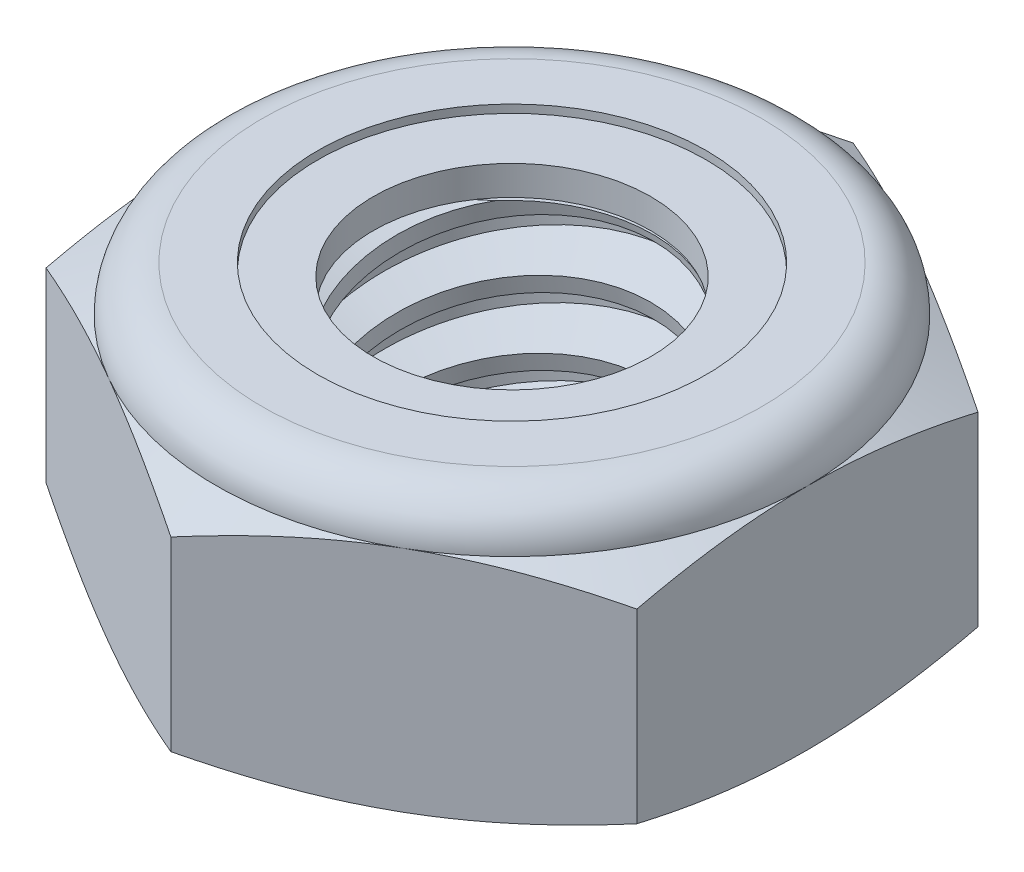
SolidWorks part; units mm, degrees
ref_plane "Front" through (0, 0, 0) normal (0, 0, 1) x (1, 0, 0)
ref_plane "Top" through (0, 0, 0) normal (0, 1, 0) x (1, 0, 0)
ref_plane "Right" through (0, 0, 0) normal (1, 0, 0) x (0, 0, -1)
sketch "Sketch1" plane through (0, 0, 0) normal (0, 1, 0) x (1, 0, 0)
  line L1 (0, 6.4158) -> (-5.5563, 3.2079)
  line L2 (-5.5563, 3.2079) -> (-5.5563, -3.2079)
  line L3 (-5.5563, -3.2079) -> (0, -6.4158)
  line L4 (0, -6.4158) -> (5.5562, -3.2079)
  line L5 (5.5562, -3.2079) -> (5.5562, 3.2079)
  line L6 (5.5562, 3.2079) -> (0, 6.4158)
  circle A0 centre (0, 0) radius 5.5563 construction
  dimension "Hex Flats" = 11.1125
extrude "Extrude1" add sketch "Sketch1" along normal blind 5.1594
sketch "Sketch2" plane through (0, 0, 0) normal (1, 0, 0) x (0, 0, -1)
  line L0 (-3.175, 0) -> (-3.175, 5.1594) construction
  line L1 (0, 0) -> (3.175, 0)
  line L2 (0, 0) -> (0, 5.1594)
  line L3 (0, 5.1594) -> (3.175, 5.1594)
  line L4 (3.175, 0) -> (3.175, 5.1594)
  line L5 (-3.2079, 5.1594) -> (3.2079, 5.1594) construction
  line L7 (0, -3.175) -> (0, 0) construction
  dimension "Thread Dia" = 6.35
revolve "Revolve1" add sketch "Sketch2" angle 360 about L7
sketch "Sketch3" plane through (0, 0, 0) normal (1, 0, 0) x (0, 0, -1)
  line L0 (3.175, 5.1594) -> (-3.175, 5.1594) construction
  line L1 (-3.175, 5.1594) -> (-3.175, 3.8894) construction
  line L2 (-3.175, 3.8894) -> (3.175, 5.1594) construction
  line L3 (3.175, 5.1594) -> (3.2061, 5.0037) construction
  line L4 (3.2061, 5.0037) -> (3.4241, 3.914)
  line L5 (3.4241, 3.914) -> (2.6722, 4.1684)
  line L6 (2.6722, 4.1684) -> (2.6099, 4.4797)
  line L7 (2.6099, 4.4797) -> (3.2061, 5.0037)
  line L8 (2.641, 4.3241) -> (3.3151, 4.4589) construction
  line L9 (3.175, 5.1594) -> (3.175, 4.4309) construction
  line L10 (3.175, 4.4309) -> (-3.175, 3.1609) construction
  line L11 (-3.175, 3.1609) -> (-3.175, 3.8894) construction
  line L12 (-0.2727, 5.1594) -> (0.2727, 2.4323) construction
  line L13 (-3.175, 0) -> (-3.175, 5.1594) construction
  line L14 (0, 5.1594) -> (3.175, 5.1594) construction
  line L15 (3.175, 0) -> (3.175, 5.1594) construction
  point P13 (0, 3.7959)
  dimension "D1" = 0.1588
  dimension "D2" = 0.3175
  dimension "Thread Pitch" = 1.27
  dimension "D4" = 60
  dimension "D5" = 1.27
revolve "Cut-Revolve1" cut sketch "Sketch3" angle 360 about L12
pattern_linear "LPattern1" count 4 spacing 1.27 along (0, -1, 0) count 2 spacing 1.27 along (0, 1, 0) of "Cut-Revolve1"
sketch "Sketch4" plane through (0, 0, 0) normal (1, 0, 0) x (0, 0, -1)
  line L0 (0, 5.1594) -> (3.175, 5.1594)
  line L1 (3.175, 5.1594) -> (2.6099, 4.8959)
  line L2 (2.6099, 4.8959) -> (2.6099, 0.2635)
  line L3 (2.6099, 0.2635) -> (3.175, 0)
  line L4 (3.175, 0) -> (0, 0)
  line L5 (0, 0) -> (0, 5.1594)
  line L6 (3.175, 0) -> (3.175, 5.1594) construction
  line L7 (0, 5.1594) -> (3.175, 5.1594) construction
  line L8 (0, 0) -> (3.175, 0) construction
  line L9 (0, 0) -> (0, 5.1594) construction
  line L10 (0, 5.1594) -> (0, 5.7829) construction
  dimension "D1" = 25
revolve "Cut-Revolve2" cut sketch "Sketch4" angle 360 about L10
combine bodies "Combine1" operation type subtract main body 112 bodies to subtract 111
sketch "Sketch5" plane through (0, 0, 0) normal (1, 0, 0) x (0, 0, -1)
  line L0 (0, 0) -> (5.5563, 0)
  line L1 (5.5563, 0) -> (6.4158, 0.4008)
  line L2 (6.4158, 0.4008) -> (6.4158, 3.8987)
  line L3 (6.4158, 3.8987) -> (5.5562, 4.2995)
  line L4 (4.6964, 5.1594) -> (4.6964, 6.4294)
  line L5 (4.6964, 6.4294) -> (7.6858, 6.4294)
  line L6 (7.6858, 6.4294) -> (7.6858, -1.27)
  line L7 (7.6858, -1.27) -> (0, -1.27)
  line L8 (0, -1.27) -> (0, 0)
  line L9 (5.5562, 4.2995) -> (5.5563, 0) construction
  line L10 (0, 0) -> (3.175, 0) construction
  line L13 (6.4158, 2.1497) -> (7.6858, 2.1497) construction
  line L14 (6.4158, 5.1594) -> (6.4158, 0) construction
  line L15 (0, 0) -> (0, 6.4294) construction
  line L20 (0, 6.4294) -> (4.6964, 6.4294) construction
  line L22 (0, 5.1594) -> (3.175, 5.1594) construction
  arc A0 (5.5562, 4.2995) -> (4.6964, 5.1594) centre (4.6964, 4.2995) ccw
  dimension "D1" = 25
  dimension "D2" = 1.27
  dimension "D3" = 5.1594
  dimension "D4" = 0.8599
revolve "Cut-Revolve3" cut sketch "Sketch5" angle 360 about L15
sketch "Sketch6" plane through (0, 0, 0) normal (1, 0, 0) x (0, 0, -1)
  line L0 (0, 4.2995) -> (5.4038, 4.2995)
  line L1 (4.6964, 5.007) -> (3.6531, 5.007)
  line L2 (0, 6.4294) -> (0, 4.2995)
  line L3 (3.6531, 6.4294) -> (0, 6.4294)
  line L4 (0, 6.4294) -> (4.6964, 6.4294) construction
  line L5 (0, 0) -> (0, 6.4294) construction
  line L6 (0, 6.4294) -> (0, 44.323) construction
  line L7 (3.6531, 5.007) -> (3.6531, 6.4294)
  line L8 (4.6964, 5.1594) -> (4.6964, 5.007) construction
  line L9 (3.6531, 5.007) -> (2.6099, 5.007) construction
  line L10 (2.6099, 5.007) -> (2.6099, 4.8959) construction
  arc A0 (5.4038, 4.2995) -> (4.6964, 5.007) centre (4.6964, 4.2995) ccw
  arc A1 (5.5562, 4.2995) -> (4.6964, 5.1594) centre (4.6964, 4.2995) ccw construction
  dimension "D1" = 0.1524
revolve "Cut-Revolve4" cut sketch "Sketch6" angle 360 about L6
sketch "Sketch7" plane through (0, 0, 0) normal (1, 0, 0) x (0, 0, -1)
  line L0 (2.6099, 4.3757) -> (5.323, 4.3757)
  line L1 (4.6964, 4.9308) -> (2.6099, 4.9308)
  line L2 (2.6099, 4.9308) -> (2.6099, 4.3757)
  line L3 (2.6099, 4.3757) -> (0, 4.3757) construction
  line L4 (0, 4.3757) -> (0, 4.9308) construction
  line L5 (0, 4.9308) -> (2.6099, 4.9308) construction
  line L6 (2.6099, 4.3757) -> (2.6099, 4.2995) construction
  line L7 (0, 4.2995) -> (5.4038, 4.2995) construction
  line L8 (4.6964, 4.9308) -> (4.6964, 5.007) construction
  arc A0 (5.323, 4.3757) -> (4.6964, 4.9308) centre (4.6964, 4.2995) ccw
  arc A2 (5.4038, 4.2995) -> (4.6964, 5.007) centre (4.6964, 4.2995) ccw construction
  dimension "D1" = 0.0762
revolve "Revolve2" add sketch "Sketch7" angle 360 about L4
equation "\"D1@Sketch3\"=\"Thread Pitch@Sketch3\"/8"
equation "\"D2@Sketch3\"=\"Thread Pitch@Sketch3\"/4"
equation "\"D5@Sketch3\"=\"Thread Pitch@Sketch3\""
equation "\"D4@LPattern1\"=\"Thread Pitch@Sketch3\""
equation "\"D3@LPattern1\"=\"Thread Pitch@Sketch3\""
equation "\"D1@LPattern1\"=\"Height@Extrude1\"/\"Thread Pitch@Sketch3\""
equation "\"D4@Sketch5\"=\"Height@Extrude1\"/6"
